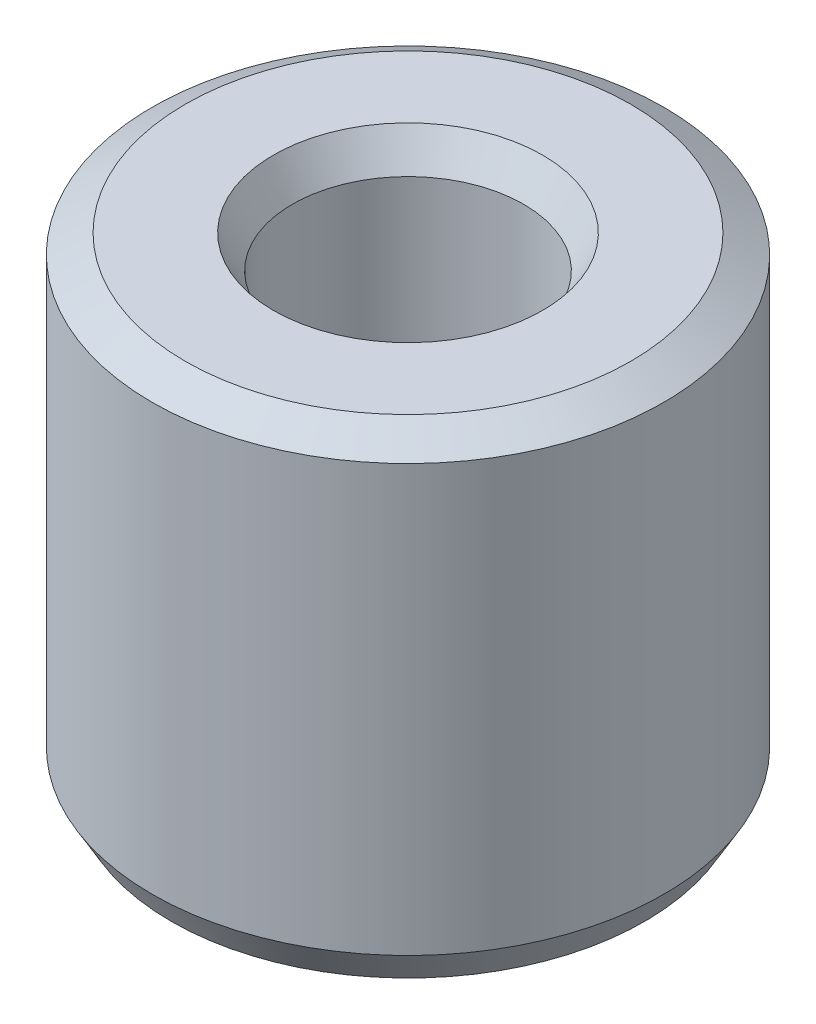
SolidWorks part; units mm, degrees
ref_plane "Front Plane" through (0, 0, 0) normal (0, 0, 1) x (1, 0, 0)
ref_plane "Top Plane" through (0, 0, 0) normal (0, 1, 0) x (1, 0, 0)
ref_plane "Right Plane" through (0, 0, 0) normal (1, 0, 0) x (0, 0, -1)
sketch "Sketch1" plane through (0, 0, 0) normal (0, 1, 0) x (1, 0, 0)
  circle A0 centre (0, 0) radius 5
  dimension "SLEEVE_OD" = 10
extrude "Boss-Extrude1" add sketch "Sketch1" along normal blind 9.3479
sketch "Sketch2" plane through (0, 0, 0) normal (0, 1, 0) x (1, 0, 0)
  circle A0 centre (0, 0) radius 2.2592
  dimension "BORE_D" = 4.5184
extrude "Cut-Extrude1" cut sketch "Sketch2" along normal through all
chamfer "Chamfer1" distance 0.3727 angle 60 4 edges at (0, 9.3479, 2.2592) (0, 0, 2.2592) (0, 0, 5) (0, 9.3479, 5) first distance on face at (0, 9.3479, 2.2592) first distance on face at (0, 0, 2.2592) first distance on face at (0, 9.3479, 5)
